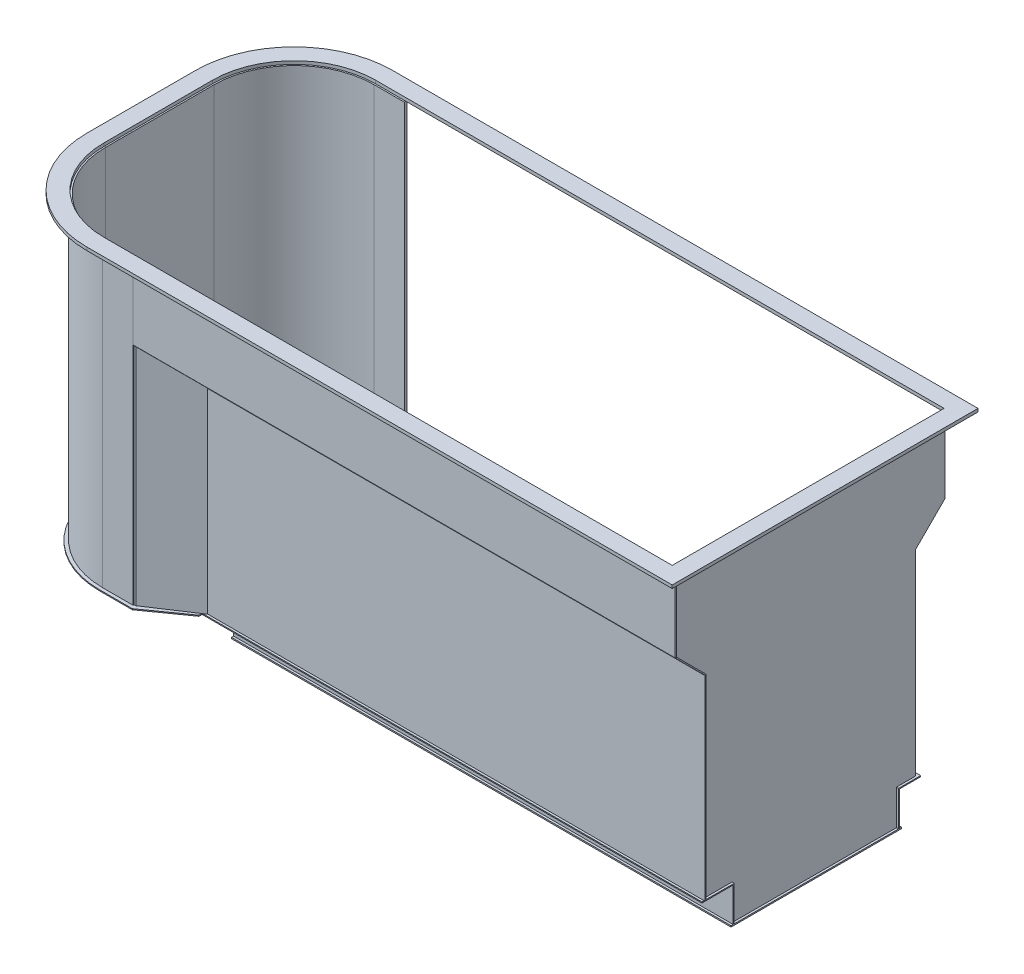
SolidWorks part; units mm, degrees
ref_plane "Front Plane" through (0, 0, 0) normal (0, 0, 1) x (1, 0, 0)
ref_plane "Top Plane" through (0, 0, 0) normal (0, 1, 0) x (1, 0, 0)
ref_plane "Right Plane" through (0, 0, 0) normal (1, 0, 0) x (0, 0, -1)
sketch "Sketch2" plane through (0, 0, 0) normal (0, 1, 0) x (1, 0, 0)
  line L0 (0, 2106.1785) -> (0, -1999.0847) construction
  line L1 (-4069.5652, 0) -> (3212.8146, 0) construction
  line L3 (-1975, 655) -> (1975, 655)
  line L4 (-1975, 655) -> (-1975, -695)
  line L5 (-1975, -695) -> (1975, -695)
  line L6 (1975, 655) -> (1975, -695)
  dimension "D1" = 3950
  dimension "D2" = 1975
  dimension "D3" = 695
  dimension "D4" = 655
  dimension "D5" = 1350
extrude "bottom 10 mm " add sketch "Sketch2" along normal blind 10 contours L3 L6 L5 L4
sketch "Sketch3" plane through (1975, 0, 0) normal (1, 0, 0) x (0, 0, -1)
  line L0 (-670, 10) -> (-670, 288)
  line L1 (655, 10) -> (-695, 10) construction
  line L2 (-670, 288) -> (-925, 288)
  line L4 (630, 10) -> (630, 288)
  line L5 (630, 288) -> (805, 288)
  line L6 (-678, 10) -> (-678, 280)
  line L7 (-678, 280) -> (-925, 280)
  line L8 (638, 10) -> (638, 280)
  line L9 (638, 280) -> (805, 280)
  line L10 (-925, 280) -> (-925, 288)
  line L11 (-678, 10) -> (-670, 10)
  line L12 (805, 288) -> (805, 280)
  line L13 (638, 10) -> (630, 10)
  dimension "D1" = 670
  dimension "D2" = 255
  dimension "D3" = 278
  dimension "D4" = 175
  dimension "D5" = 630
  dimension "D6" = 278
  dimension "D7" = 8
  dimension "D8" = 8
extrude "bend bottom 8 mm" add sketch "Sketch3" against normal blind 3950
ref_plane "Plane1" through (1950, 0, 0) normal (1, 0, 0) x (0, 0, -1)
sketch "Sketch4" plane through (1950, 0, 0) normal (1, 0, 0) x (0, 0, -1)
  line L0 (0, 0) -> (0, 3812.5627) construction
  line L1 (-1135, 2685) -> (1015, 2685)
  line L2 (1015, 2685) -> (1015, 2073)
  line L3 (1015, 2073) -> (780, 1838)
  line L4 (780, 1838) -> (780, 288)
  line L5 (780, 288) -> (630, 288)
  line L6 (-900, 288) -> (-900, 1838)
  line L7 (-900, 1838) -> (-1135, 2073)
  line L8 (-1135, 2073) -> (-1135, 2685)
  line L9 (805, 288) -> (630, 288) construction
  line L10 (630, 10) -> (-670, 10) construction
  line L11 (-670, 288) -> (-670, 10)
  line L12 (-670, 10) -> (630, 10)
  line L13 (630, 10) -> (630, 288)
  line L14 (-670, 288) -> (-900, 288)
  dimension "D1" = 780
  dimension "D2" = 900
  dimension "D3" = 235
  dimension "D4" = 235
  dimension "D5" = 235
  dimension "D6" = 235
  dimension "D7" = 612
  dimension "D8" = 612
  dimension "D9" = 1550
  dimension "D10" = 332.3402
  dimension "D11" = 2397
  dimension "D12" = 2675
extrude "back 8 mm" add sketch "Sketch4" along normal blind 8 contours L1 L2 L3 L4 L5 L13 L12 L11 L14 L6 L7 L8
sketch "Sketch5" plane through (0, 2685, 0) normal (0, 1, 0) x (1, 0, 0)
  line L0 (-2484.3019, 0) -> (2957.8112, 0) construction
  line L1 (0, 1490.2563) -> (0, -1461.0684) construction
  line L2 (-2545, 1015) -> (1950, 1015)
  line L3 (1950, 1015) -> (1950, -1135)
  line L4 (1950, -1135) -> (-2545, -1135)
  line L5 (-3190, 370) -> (-3190, -490)
  line L6 (-2545, 1149) -> (2084, 1149)
  line L7 (2084, 1149) -> (2084, -1269)
  line L8 (2084, -1269) -> (-2545, -1269)
  line L9 (-3324, 370) -> (-3324, -490)
  arc A0 (-3190, 370) -> (-2545, 1015) centre (-2545, 370) cw
  arc A1 (-3190, -490) -> (-2545, -1135) centre (-2545, -490) ccw
  arc A2 (-3324, 370) -> (-2545, 1149) centre (-2545, 370) cw
  arc A3 (-3324, -490) -> (-2545, -1269) centre (-2545, -490) ccw
  dimension "D1" = 645
  dimension "D2" = 645
  dimension "D3" = 2150
  dimension "D4" = 1015
  dimension "D5" = 1135
  dimension "D6" = 4495
  dimension "D7" = 1950
  dimension "D8" = 3190
  dimension "D9" = 134
extrude "CURB 25" add sketch "Sketch5" against normal blind 25
sketch "Sketch6" plane through (0, 2660, 0) normal (0, -1, 0) x (-1, 0, 0)
  line L0 (0, -2022.6256) -> (0, 2133.5227) construction
  line L1 (4518.6092, 0) -> (-3278.6092, 0) construction
  line L2 (-1950, -900) -> (-1950, -1135) construction
  line L3 (2545, -1135) -> (2306, -1135)
  line L4 (3190, -490) -> (3190, 370)
  line L5 (2545, 1015) -> (2306, 1015)
  line L6 (2306, -1135) -> (2306, 1015) construction
  line L7 (2545, 1023) -> (2306, 1023)
  line L8 (3198, -490) -> (3198, 370)
  line L9 (2545, -1143) -> (2306, -1143)
  arc A0 (3190, -490) -> (2545, -1135) centre (2545, -490) cw
  arc A1 (3190, 370) -> (2545, 1015) centre (2545, 370) ccw
  arc A2 (3198, 370) -> (2545, 1023) centre (2545, 370) ccw
  arc A3 (3198, -490) -> (2545, -1143) centre (2545, -490) cw
  point P11 (3190, -1135)
  point P14 (3190, 1015)
  dimension "D5" = 645
  dimension "D6" = 645
  dimension "D1" = 3190
  dimension "D2" = 2150
  dimension "D3" = 1135
  dimension "D4" = 1015
  dimension "D7" = 4256
  dimension "D8" = 239
  dimension "D9" = 8
extrude "front round" add sketch "Sketch6" along normal blind 2372 thin thin type one direction wall 12
sketch "Sketch7" plane through (0, 288, 0) normal (0, -1, 0) x (1, 0, 0)
  line L0 (-4103.7391, 0) -> (3773.798, 0) construction
  line L1 (-2545, 1135) -> (-2306, 1135) construction
  line L2 (-3190, 490) -> (-3190, -370) construction
  line L3 (-2545, -1015) -> (-2306, -1015) construction
  line L5 (0, 2114.0363) -> (0, -2020.5827) construction
  line L6 (-2545, -1049) -> (-2317.8596, -1049)
  line L7 (-3224, 490) -> (-3224, -370)
  line L8 (-2545, 1169) -> (-2285.4638, 1169)
  line L10 (-2306, 1135) -> (-1975, 900) construction
  line L11 (-1975, -805) -> (1975, -805) construction
  line L12 (-1950, 670) -> (93.0445, 670) construction
  line L13 (-1950, 668) -> (-1950, -628) construction
  line L14 (-1950, -630) -> (93.0445, -630) construction
  line L15 (93.0445, 670) -> (93.0445, -630) construction
  line L16 (-2630.7424, 60) -> (-2060.4033, 60) construction
  line L17 (-2285.4638, 1169) -> (-1977, 950)
  line L18 (-1975, 925) -> (1975, 925) construction
  line L21 (-2306, -1015) -> (-1975, -780) construction
  line L22 (-2545, -1049) -> (-2306, -1049) construction
  line L25 (-1950, 668) -> (-1950, -628)
  line L26 (-1950, 670) -> (-1975, 670) construction
  line L27 (-1975, -655) -> (-1975, 695) construction
  line L29 (-1950, -630) -> (-1975, -630) construction
  line L31 (-1977, 950) -> (-1977, 668)
  line L32 (-1977, 668) -> (-1950, 668)
  line L34 (-1950, -628) -> (-1977, -628)
  line L35 (-1977, -628) -> (-1977, -807)
  line L37 (-1950, -628) -> (-1950, -630) construction
  line L38 (-1950, 670) -> (-1950, 668) construction
  line L39 (-1975, 925) -> (-1975, 678) construction
  line L40 (-2545, 1169) -> (-2306, 1169) construction
  line L45 (-2317.8596, -1049) -> (-1977, -807)
  line L46 (-2293.9253, -1032.0074) -> (-1962.9253, -797.0074) construction
  arc A0 (-2545, -1015) -> (-3190, -370) centre (-2545, -370) cw construction
  arc A1 (-3190, 490) -> (-2545, 1135) centre (-2545, 490) cw construction
  arc A2 (-2545, -1049) -> (-3224, -370) centre (-2545, -370) cw
  arc A3 (-3224, 490) -> (-2545, 1169) centre (-2545, 490) cw
  dimension "D1" = 645
  dimension "D2" = 860
  dimension "D3" = 3190
  dimension "D4" = 1135
  dimension "D5" = 1015
  dimension "D6" = 239
  dimension "D8" = 1950
  dimension "D9" = 670
  dimension "D10" = 630
  dimension "D13" = 2
  dimension "D14" = 25
  dimension "D15" = 2
  dimension "D16" = 2
  dimension "D17" = 2
  dimension "D19" = 2
  dimension "D12" = 25
  dimension "D7" = 34
extrude "bend bottom 8 mm " add sketch "Sketch7" along normal blind 8
sketch "Sketch8" plane through (0, 280, 0) normal (0, -1, 0) x (1, 0, 0)
  line L0 (0, 0) -> (-2682.9049, 0) construction
  line L1 (-1958, 670) -> (-1950, 670)
  line L2 (-1958, 670) -> (-1958, -630)
  line L3 (-1958, -630) -> (-1950, -630)
  line L4 (-1950, 670) -> (-1950, -630)
  line L5 (0, 0) -> (0, 594.1103) construction
  dimension "D1" = 670
  dimension "D2" = 1950
  dimension "D3" = 630
  dimension "D4" = 1300
  dimension "D5" = 8
extrude "bottom lower" add sketch "Sketch8" along normal blind 270
sketch "Sketch9" plane through (0, 0, 1135) normal (0, 0, 1) x (1, 0, 0)
  line L1 (-2304, 2660) -> (1983, 2660)
  line L2 (-2304, 2660) -> (-2304, 2073)
  line L3 (-2304, 2073) -> (1983, 2073)
  line L4 (1983, 2660) -> (1983, 2073)
  line L5 (-2545, 2685) -> (2084, 2685) construction
  line L6 (-2306, 288) -> (-2306, 2660) construction
  line L7 (1958, 2073) -> (1958, 2660) construction
  dimension "D1" = 612
  dimension "D2" = 2
  dimension "D3" = 25
extrude "hv upper" add sketch "Sketch9" along normal blind 10 separate body
sketch "Sketch10" plane through (0, 469, -469) normal (0, -0.7071, 0.7071) x (1, 0, 0)
  line L0 (-2304, 2268.3986) -> (1983, 2268.3986) construction
  line L1 (1983, 2268.3986) -> (-2304, 2268.3986)
  line L2 (1983, 2268.3986) -> (1983, 1936.3986)
  line L3 (1983, 1936.3986) -> (-2304, 1936.3986)
  line L4 (-2304, 2268.3986) -> (-2304, 1936.3986)
  line L5 (-2304, 2690.5413) -> (-2304, 2275.4696) construction
  line L6 (1983, 2275.4696) -> (1983, 2690.5413) construction
  dimension "D1" = 332
extrude "hv mid" add sketch "Sketch10" along normal blind 8 separate body
sketch "Sketch11" plane through (0, 0, 900) normal (0, 0, 1) x (1, 0, 0)
  line L0 (1983, 1832.5837) -> (1983, 2067.3431) construction
  line L1 (-1950, 1832.5837) -> (1983, 1832.5837)
  line L2 (-1950, 1832.5837) -> (-1950, 288)
  line L3 (-1950, 288) -> (1983, 288)
  line L4 (1983, 1832.5837) -> (1983, 288)
  line L5 (-2304, 1832.5837) -> (1983, 1832.5837) construction
  line L6 (-1975, 288) -> (1975, 288) construction
  line L8 (1950, 288) -> (1950, 1838) construction
  dimension "D1" = 3900
extrude "HV lower" add sketch "Sketch11" along normal blind 8 separate body
sketch "Sketch12" plane through (0, 288, 0) normal (0, 1, 0) x (1, 0, 0)
  line L4 (-2306, -1135) -> (-1950, -900.2405)
  line L5 (-2291.4681, -1135) -> (-1950, -909.8234)
  line L20 (0, 0) -> (0, 1611.766) construction
  line L26 (0, 0) -> (-4021.2017, 0) construction
  line L30 (-2301.5959, -1141.6786) -> (-1945.5959, -906.9192) construction
  line L31 (-2306, -1135) -> (-2291.4681, -1135)
  line L33 (-2304, -900.2405) -> (1983, -900.2405) construction
  line L35 (-3190, 693.0369) -> (-3190, -490) construction
  line L36 (-2545, -1135) -> (-2291.4681, -1135) construction
  line L37 (-1950, 693.0369) -> (-1950, -1135) construction
  line L38 (-1950, -900.2405) -> (-1950, -909.8234)
  arc A0 (-3190, -490) -> (-2545, -1135) centre (-2545, -490) ccw construction
  dimension "D1" = 645
  dimension "D2" = 1135
  dimension "D3" = 3190
  dimension "D5" = 8
  dimension "D4" = 1950
extrude "teda wala  hv lv" add sketch "Sketch12" along normal blind 1785 separate body
